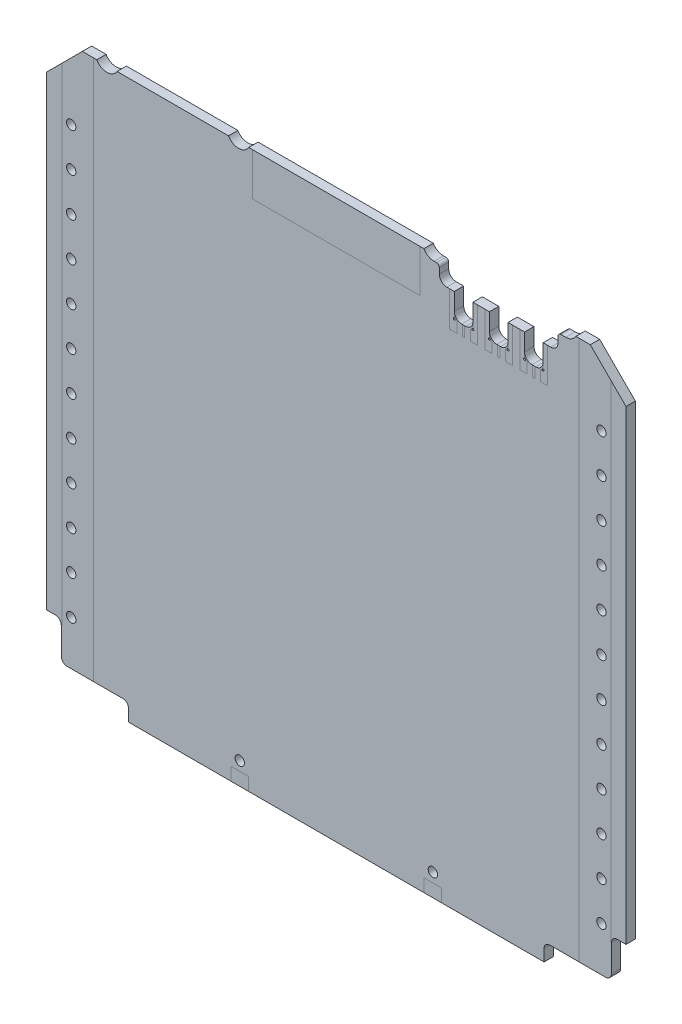
SolidWorks part; units mm, degrees
material "FR4_stuffedProtoboard"
ref_plane "Front Plane" through (0, 0, 0) normal (0, 0, 1) x (1, 0, 0)
ref_plane "Top Plane" through (0, 0, 0) normal (0, 1, 0) x (1, 0, 0)
ref_plane "Right Plane" through (0, 0, 0) normal (1, 0, 0) x (0, 0, -1)
ref_plane "Plane4" through (0, 0, -0.0125) normal (0, 0, -1) x (-1, 0, 0)
sketch "Sketch1" plane through (0, 0, -0.0125) normal (0, 0, -1) x (-1, 0, 0)
  line L4 (49.5, -50) -> (49.5, 45.3)
  line L6 (49.5, 45.3) -> (-49.5, 45.3)
  line L12 (-49.5, 45.3) -> (-49.5, -50)
  line L17 (-49.5, -50) -> (49.5, -50)
  line L18 (0, -50) -> (0, 45.3) construction
  dimension "D7" = 95.3
  dimension "D1" = 99
  dimension "D34" = 50
extrude "basicSize" add sketch "Sketch1" against normal blind 1.6
chamfer "Chamfer1" distance 6.1 angle 45 2 edges at (49.5, 45.3, 0.7875) (-49.5, 45.3, 0.7875)
sketch "Sketch4" plane through (0, 0, 1.5875) normal (0, 0, 1) x (1, 0, 0)
  line L1 (37.4679, 45.3) -> (40.9321, 45.3)
  line L7 (-43.4, 45.3) -> (43.4, 45.3) construction
  line L8 (49.5, 39.2) -> (49.5, -50) construction
  arc A0 (40.9321, 45.3) -> (37.4679, 45.3) centre (39.2, 46.3) cw
  point P5 (39.2, 44.3)
  dimension "D1" = 2
  dimension "D3" = 10.3
  dimension "D2" = 1
extrude "backplaneSideScrewCutout" cut sketch "Sketch4" against normal through all both and the other way through all
pattern_linear "LPattern3" count 2 spacing 22.5 along (-1, 0, 0) of "backplaneSideScrewCutout"
mirror "Mirror3" about plane through (0, 0, 0) normal (1, 0, 0) of "LPattern3"
sketch "Sketch6" plane through (0, 0, 1.5875) normal (0, 0, 1) x (1, 0, 0)
  line L0 (-49.5, -50) -> (-49.5, 39.2) construction
  line L1 (-49.5, -40.4) -> (-47, -40.4)
  line L2 (-49.5, -40.4) -> (-49.5, -50)
  line L4 (-47, -40.4) -> (-47, -47)
  line L5 (49.5, -50) -> (-49.5, -50) construction
  line L6 (-35.5, -50) -> (-49.5, -50)
  line L7 (-35.5, -50) -> (-35.5, -47)
  line L8 (-35.5, -47) -> (-47, -47)
  dimension "D1" = 2.5
  dimension "D2" = 3
  dimension "D3" = 9.6
  dimension "D4" = 14
extrude "Cut-Extrude4" cut sketch "Sketch6" against normal through all
fillet "Fillet1" radius 1 3 edges at (-35.5, -47, 0.7875) (-47, -47, 0.7875) (-47, -40.4, 0.7875)
mirror "Mirror1" about plane through (0, 0, 0) normal (1, 0, 0) of "Cut-Extrude4", "Fillet1"
sketch "Sketch7" plane through (0, 0, 1.5875) normal (0, 0, 1) x (1, 0, 0)
  line L0 (-14.2875, 45.5) -> (-14.2875, 39.912) construction
  line L1 (-14.2875, 45.3) -> (-14.2875, 38.007)
  line L2 (-12.2428, 38.007) -> (-11.8872, 38.007) construction
  line L3 (-14.2875, 38.007) -> (14.2875, 38.007)
  line L4 (14.2875, 45.5) -> (14.2875, 39.912) construction
  line L5 (14.2875, 45.3) -> (14.2875, 38.007)
  line L7 (-14.9679, 45.3) -> (14.9679, 45.3) construction
  line L8 (-14.2875, 45.3) -> (14.2875, 45.3)
extrude "TigerEyeFootprint" cut sketch "Sketch7" against normal blind 0.0001
sketch "thermalContacts_upper" plane through (0, 0, 1.5875) normal (0, 0, 1) x (1, 0, 0)
  line L0 (-49.5, -40.4) -> (-49.5, 39.2) construction
  line L1 (35.5, -50) -> (-35.5, -50) construction
  line L3 (-46.9, 45.3) -> (-46.9, -41.5)
  line L4 (-37.4679, 45.3) -> (-18.4321, 45.3) construction
  line L23 (-46.9, 45.3) -> (-56.3922, 45.3)
  line L24 (-56.3922, 45.3) -> (-56.3922, -41.5)
  line L25 (-56.3922, -41.5) -> (-46.9, -41.5)
  dimension "D1" = 2.6
  dimension "D2" = 8.5
extrude "keepOut_bottom" cut sketch "thermalContacts_upper" against normal blind 0.0001
sketch "Sketch3" plane through (0, 0, 1.5875) normal (0, 0, 1) x (1, 0, 0)
  line L1 (-47, -46) -> (-47, -41.5) construction
  line L2 (-36.5, -47) -> (-46, -47) construction
  line L3 (-14.9679, 45.3) -> (14.9679, 45.3) construction
  line L5 (-49.5, -40.4) -> (-49.5, 39.2) construction
  line L6 (-46.9, -41.5) -> (-46.9, 41.8) construction
  line L7 (-46.9, -41.5) -> (-47, -41.5)
  line L8 (-47, -46) -> (-47, -41.5) construction
  line L9 (-47, -41.5) -> (-46.9, -41.5) construction
  line L10 (0, -50) -> (0, 45.3) construction
  line L11 (35.5, -50) -> (-35.5, -50) construction
  line L12 (-43.4, 45.3) -> (-40.9321, 45.3) construction
  line L13 (-41.5, 45.3) -> (-46.9, 45.3)
  line L14 (-46, -47) -> (-41.5, -47)
  line L15 (-47, -41.5) -> (-47, -46)
  line L16 (-46.9, 45.3) -> (-46.9, -41.5)
  line L17 (-41.5, -47) -> (-41.5, 45.3)
  arc A3 (-47, -46) -> (-46, -47) centre (-46, -46) ccw construction
  arc A4 (-46, -47) -> (-47, -46) centre (-46, -46) cw
  dimension "D1" = 8
extrude "caution_top" cut sketch "Sketch3" against normal blind 0.0001
sketch "hold-downLocations" plane through (0, 0, 1.5875) normal (0, 0, 1) x (1, 0, 0)
  line L1 (-18, -47.8) -> (-15, -47.8) construction
  line L3 (15, -47.8) -> (18, -47.8)
  line L4 (18, -47.8) -> (18, -50)
  line L5 (35.5, -50) -> (-35.5, -50) construction
  line L6 (18, -50) -> (15, -50)
  line L7 (15, -50) -> (15, -47.8)
  line L8 (-15, -47.8) -> (-15, -50) construction
  line L9 (-15, -50) -> (-18, -50) construction
  line L10 (-18, -50) -> (-18, -47.8) construction
  line L11 (0, -50) -> (0, -47.8) construction
  line L12 (-15, -47.8) -> (15, -47.8) construction
  dimension "D1" = 3
  dimension "D2" = 2.2
  dimension "D3" = 3
  dimension "D5" = 30
extrude "hold-downFootprints" cut sketch "hold-downLocations" against normal blind 0.0001
ref_plane "midplane_Z" through (0, 0, 0.7875) normal (0, 0, 1) x (1, 0, 0)
mirror "clearances_top-bottom" about plane through (0, 0, 0.7875) normal (0, 0, 1) of "hold-downFootprints", "caution_top", "keepOut_bottom"
mirror "clearances_side-side" about plane through (0, 0, 0) normal (1, 0, 0) of "clearances_top-bottom"
sketch "Sketch10" plane through (0, 0, -0.0125) normal (0, 0, -1) x (-1, 0, 0)
  line L0 (-15, -47.8) -> (-15, -50) construction
  line L1 (-18, -47.8) -> (-15, -47.8)
  line L2 (-18, -47.8) -> (-18, -44.5)
  line L3 (-18, -44.5) -> (-15, -44.5)
  line L4 (-15, -47.8) -> (-15, -44.5)
  line L5 (-15, -50) -> (15, -50) construction
  line L6 (0, -50) -> (0, -41.5199) construction
  line L7 (15, -47.8) -> (15, -44.5)
  line L8 (18, -44.5) -> (15, -44.5)
  line L9 (18, -47.8) -> (18, -44.5)
  line L10 (18, -47.8) -> (15, -47.8)
  dimension "D1" = 5.5
extrude "bottomsideShelfKeepouts" cut sketch "Sketch10" against normal up to surface (0.0001 mm away) up to face at (16.5, -48.9, -0.0124)
sketch "recommendedBuildArea" [suppressed] plane through (0, 0, 1.5875) normal (0, 0, 1) x (1, 0, 0)
  line L0 (51.1146, 38.007) -> (51.1146, 56.8216) construction
  line L1 (-35.5, -45.5) -> (-46.8, -45.5) construction
  line L2 (-35.5, -47) -> (-35.5, -45.5) construction
  line L3 (35.5, -47) -> (35.5, -45.5) construction
  line L4 (14.2875, 45.3) -> (-14.2875, 45.3)
  line L5 (-14.2875, 45.3) -> (-14.2875, 38.007)
  line L6 (-14.2875, 38.007) -> (14.2875, 38.007)
  line L7 (-46.8, 41.9) -> (-49.5, 39.2)
  line L8 (-49.5, 39.2) -> (-49.5, -40.4)
  line L9 (-49.5, -40.4) -> (-48, -40.4)
  line L10 (-46.8, -41.5) -> (-46.8, 41.9)
  line L11 (-47, -41.4) -> (-47, -41.5)
  line L12 (-47, -41.4) -> (-47, -41.5)
  line L13 (-47, -41.5) -> (-46.8, -41.5)
  line L14 (35.5, -45.5) -> (46.8, -45.5) construction
  line L15 (54.1146, 35.007) -> (54.1146, 77.997)
  line L16 (54.1146, 77.997) -> (43.8, 42.325)
  line L17 (-46.8, -45.5) -> (-46.8, 41.9) construction
  line L20 (43.8, 42.325) -> (43.8, -42.5)
  line L21 (14.2875, 38.007) -> (14.2875, 45.3)
  line L22 (32.5, -42.5) -> (43.8, -42.5)
  line L23 (-14.2875, 45.3) -> (-14.2875, 38.007)
  line L24 (-14.2875, 38.007) -> (51.1146, 38.007)
  line L25 (32.5, -47) -> (32.5, -42.5)
  line L26 (32.5, -47) -> (32.5, -47)
  line L27 (21, -47) -> (32.5, -47)
  line L28 (21, -45) -> (21, -47)
  line L29 (46.8, -41.5) -> (47, -41.5)
  line L30 (46.8, -41.5) -> (47, -41.5)
  line L31 (46.8, 41.9) -> (46.8, -41.5)
  line L32 (48, -40.4) -> (49.5, -40.4)
  line L33 (49.5, -40.4) -> (49.5, 39.2)
  line L34 (49.5, 39.2) -> (46.8, 41.9)
  line L35 (47, -41.5) -> (47, -41.4)
  line L36 (12, -45) -> (21, -45)
  line L37 (47, -41.5) -> (47, -41.4)
  line L38 (46.8, 41.9) -> (46.8, -45.5) construction
  line L39 (12, -47) -> (12, -45)
  line L40 (-12, -47) -> (12, -47)
  line L41 (-12, -45) -> (-12, -47)
  line L42 (-21, -45) -> (-12, -45)
  line L43 (-21, -47) -> (-21, -45)
  line L44 (-32.5, -47) -> (-21, -47)
  line L45 (-32.5, -47) -> (-32.5, -47)
  line L46 (-32.5, -47) -> (-32.5, -42.5)
  line L47 (-32.5, -42.5) -> (-43.8, -42.5)
  line L48 (-43.8, -42.5) -> (-43.8, 34.7661)
  line L49 (-43.8, 34.7661) -> (-43.8, 34.7661)
  line L50 (-43.8, 34.7661) -> (-39.8793, 42.3)
  line L51 (-17.2875, 42.3) -> (-39.8793, 42.3)
  line L52 (-17.2875, 42.3) -> (-17.2875, 35.007)
  line L53 (-17.2875, 35.007) -> (54.1146, 35.007)
  line L59 (-47, -41.5) -> (-46.8, -41.5)
  line L72 (-15, -48) -> (-15, -50)
  line L73 (-15, -50) -> (15, -50)
  line L74 (15, -50) -> (15, -48)
  line L75 (15, -48) -> (18, -48)
  line L76 (18, -48) -> (18, -50)
  line L77 (18, -50) -> (35.5, -50)
  line L78 (35.5, -50) -> (35.5, -48)
  line L79 (36.5, -47) -> (41.5, -47)
  line L80 (41.5, -47) -> (41.5, 45.3)
  line L81 (41.5, 45.3) -> (40.9321, 45.3)
  line L82 (37.4679, 45.3) -> (34.25, 45.3)
  line L83 (34.25, 45.3) -> (34.25, 38.35)
  line L84 (34.25, 38.35) -> (30.75, 38.35)
  line L85 (30.75, 38.35) -> (30.75, 45.3)
  line L86 (30.75, 45.3) -> (29.25, 45.3)
  line L87 (29.25, 45.3) -> (29.25, 38.35)
  line L88 (29.25, 38.35) -> (25.75, 38.35)
  line L89 (25.75, 38.35) -> (25.75, 45.3)
  line L90 (25.75, 45.3) -> (24.25, 45.3)
  line L91 (24.25, 45.3) -> (24.25, 38.35)
  line L92 (24.25, 38.35) -> (20.75, 38.35)
  line L93 (20.75, 38.35) -> (20.75, 45.3)
  line L94 (20.75, 45.3) -> (18.4321, 45.3)
  line L95 (14.9679, 45.3) -> (14.2875, 45.3)
  line L96 (14.2875, 45.3) -> (14.2875, 38.007)
  line L97 (14.2875, 38.007) -> (-14.2875, 38.007)
  line L98 (-14.2875, 38.007) -> (-14.2875, 45.3)
  line L99 (-14.2875, 45.3) -> (-14.9679, 45.3)
  line L100 (-18.4321, 45.3) -> (-37.4679, 45.3)
  line L101 (-40.9321, 45.3) -> (-41.5, 45.3)
  line L102 (41.5, -47) -> (41.5, 45.3)
  line L103 (-41.5, -47) -> (-36.5, -47)
  line L104 (-35.5, -48) -> (-35.5, -50)
  line L105 (-35.5, -50) -> (-18, -50)
  line L106 (-18, -50) -> (-18, -48)
  line L107 (-18, -48) -> (-15, -48)
  line L108 (-15, -48) -> (-15, -50) construction
  line L109 (-15, -50) -> (15, -50) construction
  line L110 (15, -50) -> (15, -48) construction
  line L111 (15, -48) -> (18, -48) construction
  line L112 (18, -48) -> (18, -50) construction
  line L113 (18, -50) -> (35.5, -50) construction
  line L114 (35.5, -50) -> (35.5, -47) construction
  line L115 (35.5, -47) -> (41.5, -47) construction
  line L133 (51.1146, 38.007) -> (-14.2875, 38.007)
  line L134 (-14.2875, 38.007) -> (-14.2875, 45.3)
  line L136 (-14.2875, 45.3) -> (-41.7, 45.3) construction
  line L139 (-41.5, -47) -> (-35.5, -47) construction
  line L140 (-35.5, -47) -> (-35.5, -50) construction
  line L141 (-35.5, -50) -> (-18, -50) construction
  line L142 (-18, -50) -> (-18, -48) construction
  line L143 (-18, -48) -> (-15, -48) construction
  line L144 (-46.8, 35.5) -> (-41.7, 45.3) construction
  line L160 (-41.5, 45.3) -> (-41.5, -47)
  line L161 (-41.5, 45.3) -> (-41.5, -47)
  line L162 (-46.8, 41.9) -> (-46.8, 35.5) construction
  line L163 (51.1146, 56.8216) -> (46.8, 41.9) construction
  arc A1 (-47, -41.4) -> (-48, -40.4) centre (-48, -41.4) ccw
  arc A3 (48, -40.4) -> (47, -41.4) centre (48, -41.4) ccw
  arc A10 (36.5, -47) -> (35.5, -48) centre (36.5, -48) ccw
  arc A11 (37.4679, 45.3) -> (40.9321, 45.3) centre (39.2, 46.3) ccw
  arc A12 (14.9679, 45.3) -> (18.4321, 45.3) centre (16.7, 46.3) ccw
  arc A13 (-18.4321, 45.3) -> (-14.9679, 45.3) centre (-16.7, 46.3) ccw
  arc A14 (-40.9321, 45.3) -> (-37.4679, 45.3) centre (-39.2, 46.3) ccw
  arc A15 (-35.5, -48) -> (-36.5, -47) centre (-36.5, -48) ccw
  dimension "D5" = 1.5
  dimension "D1" = 0
  dimension "D2" = 0
  dimension "D3" = 0
  dimension "D4" = 0
  dimension "D6" = 3
sketch "Sketch17" [suppressed] plane through (0, 0, 1.5875) normal (0, 0, 1) x (1, 0, 0)
  line L0 (-49.5, 39.2) -> (0, 88.7) construction
  line L1 (0, 88.7) -> (49.5, 39.2) construction
  line L2 (-49.5, 39.2) -> (-46.9, 41.8) construction
  line L3 (46.9, 41.8) -> (49.5, 39.2) construction
  point P0 (0, 0.2)
  dimension "D2" = 88.5
ref_point "rail midpoint"
sketch "locatorSketch" plane through (0, 0, 1.5875) normal (0, 0, 1) x (1, 0, 0)
  line L0 (-12.2428, 39.531) -> (12.2428, 38.007) construction
  line L1 (12.2428, 39.531) -> (-12.2428, 38.007) construction
  line L2 (-21.9628, 39.277) -> (-33.0372, 38.261) construction
  line L3 (-33.0372, 39.277) -> (-21.9628, 38.261) construction
  line L4 (-12.2428, 38.261) -> (-12.2428, 38.007)
  line L5 (-11.8872, 38.261) -> (-12.2428, 38.261)
  line L6 (-11.8872, 38.007) -> (-11.8872, 38.261)
  line L7 (-12.2428, 38.007) -> (-11.8872, 38.007)
  line L8 (-12.2428, 38.261) -> (-12.2428, 38.007)
  line L9 (-11.8872, 38.261) -> (-12.2428, 38.261)
  line L10 (-11.8872, 38.007) -> (-11.8872, 38.261)
  line L11 (-12.2428, 38.007) -> (-11.8872, 38.007)
  line L12 (-12.2428, 39.531) -> (-12.2428, 39.277)
  line L13 (-11.8872, 39.531) -> (-12.2428, 39.531)
  line L14 (-11.8872, 39.277) -> (-11.8872, 39.531)
  line L15 (-12.2428, 39.277) -> (-11.8872, 39.277)
  line L16 (-12.2428, 39.531) -> (-12.2428, 39.277)
  line L17 (-11.8872, 39.531) -> (-12.2428, 39.531)
  line L18 (-11.8872, 39.277) -> (-11.8872, 39.531)
  line L19 (-12.2428, 39.277) -> (-11.8872, 39.277)
  line L20 (11.8872, 39.531) -> (11.8872, 39.277)
  line L21 (12.2428, 39.531) -> (11.8872, 39.531)
  line L22 (12.2428, 39.277) -> (12.2428, 39.531)
  line L23 (11.8872, 39.277) -> (12.2428, 39.277)
  line L24 (11.8872, 39.531) -> (11.8872, 39.277)
  line L25 (12.2428, 39.531) -> (11.8872, 39.531)
  line L26 (12.2428, 39.277) -> (12.2428, 39.531)
  line L27 (11.8872, 39.277) -> (12.2428, 39.277)
  line L28 (11.8872, 38.261) -> (11.8872, 38.007)
  line L29 (12.2428, 38.261) -> (11.8872, 38.261)
  line L30 (12.2428, 38.007) -> (12.2428, 38.261)
  line L31 (11.8872, 38.007) -> (12.2428, 38.007)
  line L32 (11.8872, 38.261) -> (11.8872, 38.007)
  line L33 (12.2428, 38.261) -> (11.8872, 38.261)
  line L34 (12.2428, 38.007) -> (12.2428, 38.261)
  line L35 (11.8872, 38.007) -> (12.2428, 38.007)
  line L38 (-21.9628, 39.531) -> (-21.9628, 39.277)
  line L39 (-21.6072, 39.531) -> (-21.9628, 39.531)
  line L40 (-21.6072, 39.277) -> (-21.6072, 39.531)
  line L41 (-21.9628, 39.277) -> (-21.6072, 39.277)
  line L42 (-21.9628, 39.531) -> (-21.9628, 39.277)
  line L43 (-21.6072, 39.531) -> (-21.9628, 39.531)
  line L44 (-21.6072, 39.277) -> (-21.6072, 39.531)
  line L45 (-21.9628, 39.277) -> (-21.6072, 39.277)
  line L46 (-33.3928, 38.261) -> (-33.3928, 38.007)
  line L47 (-33.0372, 38.261) -> (-33.3928, 38.261)
  line L48 (-33.0372, 38.007) -> (-33.0372, 38.261)
  line L49 (-33.3928, 38.007) -> (-33.0372, 38.007)
  line L50 (-33.3928, 38.261) -> (-33.3928, 38.007)
  line L51 (-33.0372, 38.261) -> (-33.3928, 38.261)
  line L52 (-33.0372, 38.007) -> (-33.0372, 38.261)
  line L53 (-33.3928, 38.007) -> (-33.0372, 38.007)
  line L55 (-21.9628, 38.261) -> (-21.9628, 38.007)
  line L56 (-21.6072, 38.261) -> (-21.9628, 38.261)
  line L57 (-21.6072, 38.007) -> (-21.6072, 38.261)
  line L58 (-21.9628, 38.007) -> (-21.6072, 38.007)
  line L59 (-21.9628, 38.261) -> (-21.9628, 38.007)
  line L60 (-21.6072, 38.261) -> (-21.9628, 38.261)
  line L61 (-21.6072, 38.007) -> (-21.6072, 38.261)
  line L62 (-21.9628, 38.007) -> (-21.6072, 38.007)
  line L63 (-33.3928, 39.531) -> (-33.3928, 39.277)
  line L64 (-33.0372, 39.531) -> (-33.3928, 39.531)
  line L65 (-33.0372, 39.277) -> (-33.0372, 39.531)
  line L66 (-33.3928, 39.277) -> (-33.0372, 39.277)
  line L67 (-33.3928, 39.531) -> (-33.3928, 39.277)
  line L68 (-33.0372, 39.531) -> (-33.3928, 39.531)
  line L69 (-33.0372, 39.277) -> (-33.0372, 39.531)
  line L70 (-33.3928, 39.277) -> (-33.0372, 39.277)
  dimension "D1" = 0
  dimension "D2" = 0
  dimension "D3" = 0
  dimension "D4" = 0
  dimension "D5" = 0
  dimension "D6" = 0
  dimension "D7" = 0
  dimension "D8" = 0
sketch "Sketch8" plane through (0, 0, 1.5875) normal (0, 0, 1) x (1, 0, 0)
  line L0 (-49.5, -40.4) -> (-48, -40.4) construction
  line L2 (-49.5, -40.4) -> (-49.5, 39.2) construction
  line L3 (-41.5, 45.3) -> (-43.4, 45.3) construction
  line L4 (-18, -47.8) -> (-15, -47.8) construction
  line L5 (-45.3, 33.5) -> (-46.9, 33.5) construction
  line L6 (-46.9, 41.8) -> (-46.9, -41.5) construction
  line L7 (-16.5, -46.2) -> (-16.5, -47.8) construction
  line L8 (-18, -47.8) -> (-15, -47.8) construction
  circle A0 centre (-45.3, 33.5) radius 0.8
  circle A1 centre (-45.3, 26.8727) radius 0.8
  circle A2 centre (-45.3, 20.2455) radius 0.8
  circle A3 centre (-45.3, 13.6182) radius 0.8
  circle A4 centre (-45.3, 6.9909) radius 0.8
  circle A5 centre (-45.3, 0.3636) radius 0.8
  circle A6 centre (-45.3, -6.2636) radius 0.8
  circle A7 centre (-45.3, -12.8909) radius 0.8
  circle A8 centre (-45.3, -19.5182) radius 0.8
  circle A9 centre (-45.3, -26.1455) radius 0.8
  circle A10 centre (-45.3, -32.7727) radius 0.8
  circle A11 centre (-45.3, -39.4) radius 0.8
  circle A12 centre (-16.5, -46.2) radius 0.8
  point P35 (-16.5, -47.8)
  dimension "D1" = 1.6
  dimension "D3" = 1
  dimension "D5" = 4.2
  dimension "D6" = 11.8
  dimension "D2" = 12
extrude "springPinHoleSeed" cut sketch "Sketch8" against normal blind 10
mirror "Mirror4" about plane through (0, 0, 0) normal (1, 0, 0) of "springPinHoleSeed"
sketch "Sketch9" plane through (0, 0, 1.5875) normal (0, 0, 1) x (1, 0, 0)
  circle A0 centre (-45.3, 33.5) radius 1.35
  dimension "D1" = 2.7
sketch "bottomsideKeepout_trace" plane through (0, 0, -0.0125) normal (0, 0, -1) x (-1, 0, 0)
  line L0 (18, -50) -> (18, -44.5) construction
  line L1 (18, -44.5) -> (15, -44.5) construction
  line L2 (15, -44.5) -> (15, -50) construction
  line L3 (-15, -44.5) -> (-15, -50) construction
  line L4 (-15, -44.5) -> (-18, -44.5) construction
  line L5 (-18, -50) -> (-18, -44.5) construction
  line L6 (18, -50) -> (18, -44.5)
  line L7 (18, -44.5) -> (15, -44.5)
  line L8 (15, -44.5) -> (15, -50)
  line L9 (-15, -44.5) -> (-15, -50)
  line L10 (-15, -44.5) -> (-18, -44.5)
  line L11 (-18, -50) -> (-18, -44.5)
  line L12 (15, -50) -> (18, -50) construction
  line L13 (-15, -50) -> (-18, -50) construction
  line L14 (15, -50) -> (18, -50)
  line L15 (-15, -50) -> (-18, -50)
sketch "Sketch11" plane through (0, 0, 1.5875) normal (0, 0, 1) x (1, 0, 0)
  line L0 (49.5, 39.2) -> (49.5, -40.4) construction
  line L6 (35.34, 41.56) -> (32.16, 41.56)
  line L8 (35.34, 41.56) -> (35.34, 37.36)
  line L11 (35.34, 37.36) -> (32.16, 37.36)
  line L12 (32.16, 41.56) -> (32.16, 37.36)
  line L13 (35.34, 41.56) -> (32.16, 37.36) construction
  line L14 (35.34, 37.36) -> (32.16, 41.56) construction
  line L18 (29.34, 41.56) -> (26.16, 41.56)
  line L19 (29.34, 41.56) -> (29.34, 37.36)
  line L20 (29.34, 37.36) -> (26.16, 37.36)
  line L21 (26.16, 41.56) -> (26.16, 37.36)
  line L22 (29.34, 41.56) -> (26.16, 37.36) construction
  line L23 (29.34, 37.36) -> (26.16, 41.56) construction
  line L24 (23.34, 41.56) -> (20.16, 41.56)
  line L25 (23.34, 41.56) -> (23.34, 37.36)
  line L26 (23.34, 37.36) -> (20.16, 37.36)
  line L27 (20.16, 41.56) -> (20.16, 37.36)
  line L28 (23.34, 41.56) -> (20.16, 37.36) construction
  line L29 (23.34, 37.36) -> (20.16, 41.56) construction
  line L30 (18.4321, 45.3) -> (37.4679, 45.3) construction
  line L31 (16.7, 46.3) -> (39.2, 46.3) construction
  point P4 (33.75, 39.46)
  point P10 (27.95, 46.3)
  point P15 (27.75, 39.46)
  point P20 (21.75, 39.46)
  dimension "D5" = 6
  dimension "D1" = 3.18
  dimension "D2" = 4.2
  dimension "D3" = 21.75
  dimension "D4" = 3
  dimension "D6" = 3.74
extrude "Cut-Extrude5" cut sketch "Sketch11" against normal blind 10
fillet "Fillet2" radius 1.27 6 edges at (23.34, 37.36, 0.7875) (29.34, 37.36, 0.7875) (35.34, 37.36, 0.7875) (32.16, 37.36, 0.7875) (26.16, 37.36, 0.7875) (20.16, 37.36, 0.7875)
hole_wizard "Ø0.32 (0.32) Diameter Hole1" positions "Sketch12" profile "Sketch13" hole size "Ø0.32" standard "ANSI Metric"
sketch "Sketch12" plane through (0, 0, 1.5875) normal (0, 0, 1) x (1, 0, 0)
  line L1 (35.34, 38.63) -> (35.34, 41.56) construction
  line L2 (32.16, 41.56) -> (32.16, 38.63) construction
  line L3 (33.75, 37.36) -> (34.7997, 37.36) construction
  line L4 (33.43, 37.36) -> (34.07, 37.36) construction
  point P0 (35.34, 37.52)
  point P2 (32.16, 37.52)
  point P16 (29.34, 37.52)
  point P17 (26.16, 37.52)
  point P18 (23.34, 37.52)
  point P19 (20.16, 37.52)
  dimension "D2" = 6
  dimension "D3" = 0.16
  dimension "D1" = 3
sketch "Sketch13" plane through (35.34, 37.52, 1.5875) normal (1, 0, 0) x (0, -1, 0)
  line L0 (0, 0) -> (0, 9.6211)
  line L1 (0, 9.6211) -> (0.16, 9.525)
  line L2 (0.16, 9.525) -> (0.16, 0)
  line L5 (0.16, 0) -> (0, 0)
  line L10 (0, 9.6211) -> (-0.16, 9.525) construction
  line L11 (0, -6.35) -> (0, 107.95) construction
  dimension "Hole Dia." = 0.32
  dimension "Hole Depth" = 9.525
  dimension "Drill Angle" = 118
sketch "Sketch14" plane through (0, 0, 1.5875) normal (0, 0, 1) x (1, 0, 0)
  line L1 (36.125, 41.56) -> (35.34, 41.56)
  line L2 (36.125, 41.56) -> (36.125, 35.57)
  line L3 (36.125, 35.57) -> (34.895, 35.57)
  line L4 (31.375, 41.56) -> (31.375, 35.57)
  line L5 (36.125, 41.56) -> (31.375, 35.57) construction
  line L6 (36.125, 35.57) -> (31.375, 41.56) construction
  line L7 (33.75, 37.36) -> (33.75, 35.57) construction
  line L8 (33.43, 37.36) -> (34.07, 37.36) construction
  line L9 (32.605, 35.57) -> (32.605, 37.36)
  line L10 (33.56, 37.36) -> (33.94, 37.36)
  line L11 (33.56, 37.36) -> (33.56, 35.57)
  line L12 (33.56, 35.57) -> (33.94, 35.57)
  line L13 (33.94, 37.36) -> (33.94, 35.57)
  line L14 (33.56, 37.36) -> (33.94, 35.57) construction
  line L15 (33.56, 35.57) -> (33.94, 37.36) construction
  line L16 (34.895, 35.57) -> (34.895, 37.36)
  line L17 (33.94, 35.57) -> (33.56, 35.57)
  line L18 (32.16, 41.56) -> (32.16, 38.63) construction
  line L19 (35.34, 38.63) -> (35.34, 41.56) construction
  line L20 (32.16, 41.56) -> (32.16, 38.63)
  line L21 (35.34, 38.63) -> (35.34, 41.56)
  line L22 (33.56, 37.36) -> (33.94, 37.36)
  line L23 (32.16, 41.56) -> (31.375, 41.56)
  line L24 (32.605, 37.36) -> (32.16, 37.36)
  line L25 (34.895, 37.36) -> (35.34, 37.36)
  line L26 (32.16, 37.68) -> (32.16, 38.63)
  line L27 (35.34, 37.68) -> (35.34, 38.63)
  line L28 (32.605, 35.57) -> (31.375, 35.57)
  circle A2 centre (32.16, 37.52) radius 0.16 construction
  circle A3 centre (35.34, 37.52) radius 0.16 construction
  arc A6 (32.16, 37.68) -> (32.16, 37.36) centre (32.16, 37.52) ccw
  arc A7 (35.34, 37.36) -> (35.34, 37.68) centre (35.34, 37.52) ccw
  point P4 (33.75, 38.565)
  point P15 (33.75, 36.465)
  dimension "D1" = 5.99
  dimension "D2" = 4.75
  dimension "D3" = 2.29
  dimension "D4" = 0.38
extrude "Boss-Extrude1" add sketch "Sketch14" along normal blind 0.0001 contours A6 L26 L20 L23 L4 L28 L9 L24 | L13 L10 L11 L12 | A7 L25 L16 L3 L2 L1 L21 L27 region at (35.6451, 38.2662, 1.5875) region at (31.8549, 38.2662, 1.5875) region at (33.75, 36.465, 1.5875)
pattern_linear "LPattern4" count 3 spacing 6 along (-1, 0, 0) of "Boss-Extrude1"
sketch "Sketch15" plane through (0, 0, 1.5875) normal (0, 0, 1) x (1, 0, 0)
  line L0 (18.4321, 45.3) -> (37.4679, 45.3) construction
  line L1 (17.605, 45.3) -> (37.895, 45.3)
  line L2 (17.605, 44.3) -> (17.605, 42.83)
  line L3 (18.875, 41.56) -> (36.625, 41.56)
  line L4 (37.895, 44.3) -> (37.895, 42.83)
  line L5 (17.605, 45.3) -> (37.895, 41.56) construction
  line L6 (17.605, 41.56) -> (37.895, 45.3) construction
  line L7 (35.34, 41.56) -> (32.16, 41.56) construction
  line L8 (19.375, 41.56) -> (19.375, 35.57) construction
  line L9 (36.125, 41.56) -> (36.125, 35.57) construction
  line L11 (37.895, 45.3) -> (39.2, 45.3)
  line L13 (37.895, 44.3) -> (39.2, 44.3)
  line L14 (39.2, 45.3) -> (39.2, 44.3)
  line L15 (37.895, 45.3) -> (39.2, 44.3) construction
  line L16 (37.895, 44.3) -> (39.2, 45.3) construction
  line L17 (16.7, 44.3) -> (17.605, 44.3)
  line L18 (16.7, 44.3) -> (16.7, 45.3)
  line L19 (16.7, 45.3) -> (17.605, 45.3)
  line L21 (16.7, 44.3) -> (17.605, 45.3) construction
  line L22 (16.7, 45.3) -> (17.605, 44.3) construction
  arc A0 (36.625, 41.56) -> (37.895, 42.83) centre (36.625, 42.83) ccw
  arc A1 (17.605, 42.83) -> (18.875, 41.56) centre (18.875, 42.83) ccw
  arc A5 (37.4679, 45.3) -> (40.9321, 45.3) centre (39.2, 46.3) ccw construction
  arc A6 (14.9679, 45.3) -> (18.4321, 45.3) centre (16.7, 46.3) ccw construction
  point P4 (27.75, 43.43)
  point P22 (38.5475, 44.8)
  point P28 (17.1525, 44.8)
  dimension "D3" = 1.27
  dimension "D1" = 0.5
  dimension "D2" = 0.5
extrude "Cut-Extrude6" cut sketch "Sketch15" against normal through all and the other way through all
fillet "Fillet3" radius 0.5 2 edges at (17.605, 44.3, 0.7875) (37.895, 44.3, 0.7875)
sketch "Sketch16" [suppressed] plane through (0, 0, 1.5875) normal (0, 0, 1) x (1, 0, 0)
  line L0 (-54.5, 7.575) -> (-48, 7.575)
  line L2 (-47, 6.575) -> (-47, -6.175)
  line L4 (-54.5, 7.575) -> (-54.5, -7.175)
  line L5 (-54.5, 0.2) -> (0, 0.2) construction
  line L6 (-54.5, -7.175) -> (-48, -7.175)
  line L7 (-49.5, -40.4) -> (-49.5, 39.2) construction
  arc A0 (-48, 7.575) -> (-47, 6.575) centre (-48, 6.575) cw
  circle A2 centre (-42.3, 5.585) radius 0.8
  arc A3 (-48, -7.175) -> (-47, -6.175) centre (-48, -6.175) ccw
  circle A4 centre (-42.3, -5.185) radius 0.8
  point P17 (-47, 0.2)
  dimension "D3" = 1.6
  dimension "D5" = 1
  dimension "D1" = 14.75
  dimension "D2" = 10.77
  dimension "D4" = 47
  dimension "D6" = 42.3
  dimension "D7" = 5
extrude "Cut-Extrude7" [suppressed] cut sketch "Sketch16" against normal through all both and the other way through all
ref_axis "Axis1" [suppressed] through (0, 0.2, 1.5875) along (0, 0, 1)
pattern_circular "CirPattern1" [suppressed] count 4 over 360 about axis through (0, 0.2, 1.5875) along (0, 0, 1) of bodies 131
